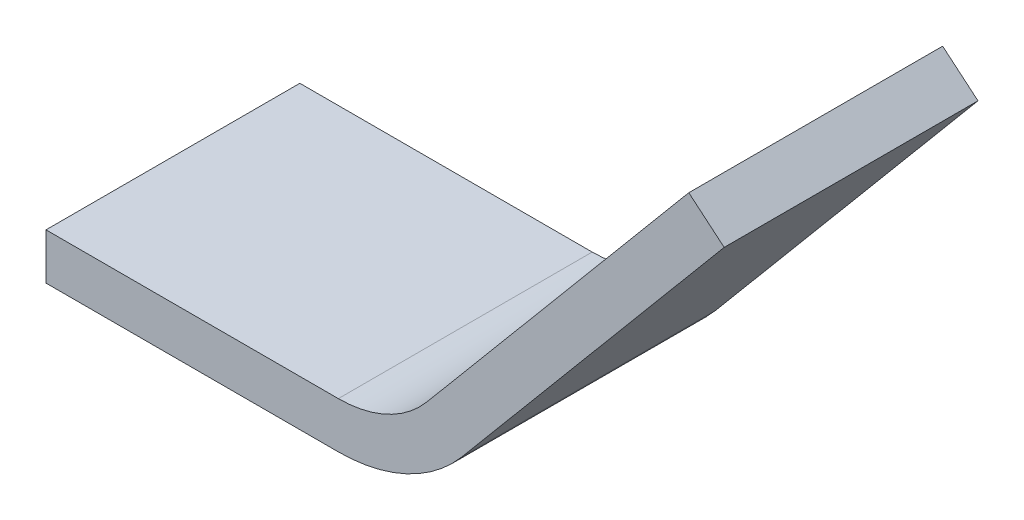
SolidWorks part; units mm, degrees
ref_plane "Plan de face" through (0, 0, 0) normal (0, 0, 1) x (1, 0, 0)
ref_plane "Plan de dessus" through (0, 0, 0) normal (0, 1, 0) x (1, 0, 0)
ref_plane "Plan de droite" through (0, 0, 0) normal (1, 0, 0) x (0, 0, -1)
sketch "Esquisse1" plane through (0, 0, 0) normal (0, 0, 1) x (1, 0, 0)
  line L0 (-0.4663, 0) -> (-3, 0)
  line L1 (0.2997, 0.3572) -> (2.5712, 3.0642)
  arc A0 (-0.4663, 0) -> (0.2997, 0.3572) centre (-0.4663, 1) ccw
  point P5 (0, 0)
  point P7 (0, 0)
  dimension "D4" = 1
  dimension "D1" = 50
  dimension "D2" = 4
  dimension "D3" = 3
extrude "Extru.-Mince1" add sketch "Esquisse1" along normal blind 2.2 thin thin type one direction wall 0.4
